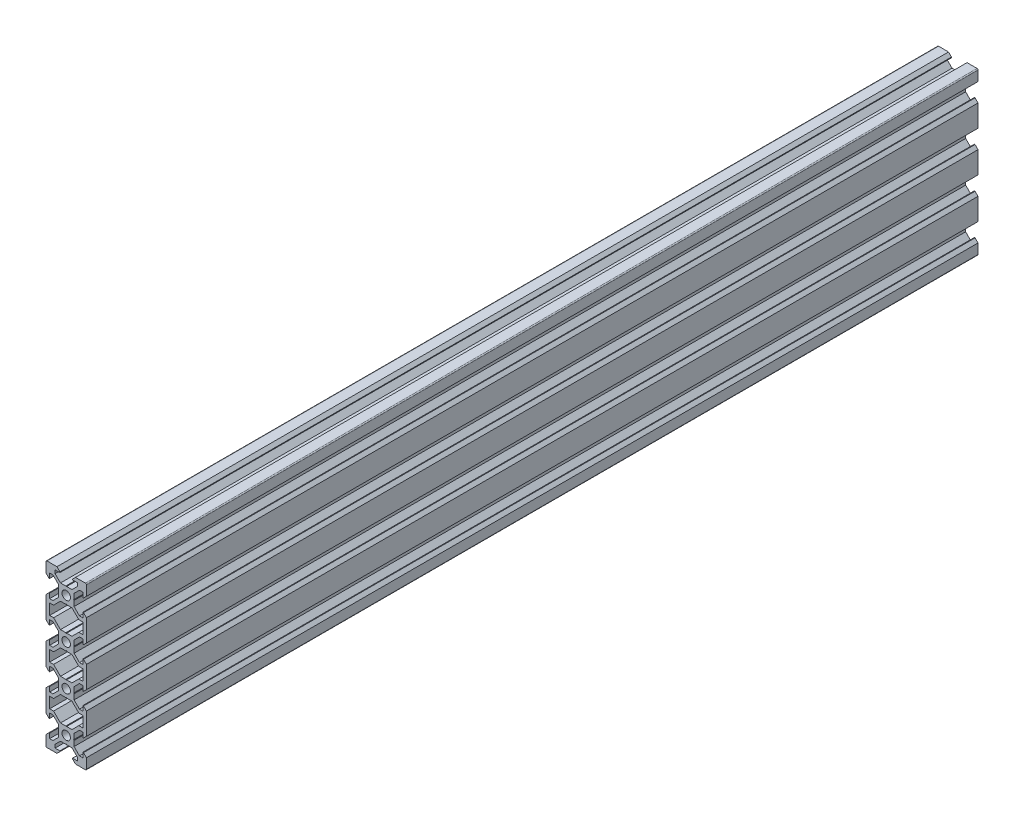
SolidWorks part; units mm, degrees
ref_plane "Plan de face" through (0, 0, 0) normal (0, 0, 1) x (1, 0, 0)
ref_plane "Plan de dessus" through (0, 0, 0) normal (0, 1, 0) x (1, 0, 0)
ref_plane "Plan de droite" through (0, 0, 0) normal (1, 0, 0) x (0, 0, -1)
ref_axis "Axe" through (0, 0, -13.782) along (0, 0, 1)
sketch "Esquisse1" plane through (0, 0, 0) normal (0, 0, 1) x (1, 0, 0)
  line L0 (0, 27.6392) -> (0, -27.6392) construction
  line L1 (-33.6074, 0) -> (33.6074, 0) construction
  line L2 (0, 0) -> (-22.2114, 22.2114) construction
  line L3 (-9.5, 10) -> (-4.58, 10)
  line L4 (-4.58, 10) -> (-3.125, 8.545)
  line L5 (-3.125, 8.545) -> (-3.125, 8.2)
  line L6 (-3.125, 8.2) -> (-5.5, 8.2)
  line L7 (-2.8393, 3.9) -> (-5.5, 6.5607)
  line L8 (-2.8393, 3.9) -> (-0.21, 3.9)
  line L9 (-5.5, 6.5607) -> (-5.5, 8.2)
  line L10 (0, 3.69) -> (0, 2.1)
  line L11 (-3.9, 2.8393) -> (-6.5607, 5.5)
  line L12 (-8.545, 3.125) -> (-8.2, 3.125)
  line L13 (-8.2, 3.125) -> (-8.2, 5.5)
  line L14 (-6.5607, 5.5) -> (-8.2, 5.5)
  line L15 (-10, 4.58) -> (-8.545, 3.125)
  line L16 (-10, 9.5) -> (-10, 4.58)
  line L17 (-0.21, 3.9) -> (0, 3.69)
  line L18 (-3.9, 2.8393) -> (-3.9, 0.21)
  line L19 (-6.2393, -12.7) -> (-8.2, -12.7)
  line L20 (-3.9, 0.21) -> (-3.69, 0)
  line L21 (-0.21, -3.9) -> (0, -3.69)
  line L22 (0, -3.69) -> (0, -2.1)
  line L23 (-6.5607, -5.5) -> (-8.2, -5.5)
  line L24 (-2.8393, -3.9) -> (-0.21, -3.9)
  line L25 (-8.545, -3.125) -> (-8.2, -3.125)
  line L26 (-10, -4.58) -> (-8.545, -3.125)
  line L27 (-8.2, -3.125) -> (-8.2, -5.5)
  line L28 (-2.8393, -3.9) -> (-6.2393, -7.3)
  line L29 (-3.9, -2.8393) -> (-6.5607, -5.5)
  line L30 (-3.9, -2.8393) -> (-3.9, -0.21)
  line L31 (-3.9, -0.21) -> (-3.69, 0)
  line L32 (-6.2393, -7.3) -> (-8.2, -7.3)
  line L33 (-8.2, -7.3) -> (-8.2, -12.7)
  line L34 (-8.2, -10) -> (-10, -10) construction
  line L35 (-10, -15.42) -> (-10, -4.58)
  line L36 (-3.9, -19.79) -> (-3.69, -20)
  line L37 (-3.9, -17.1607) -> (-3.9, -19.79)
  line L38 (-3.9, -17.1607) -> (-6.5607, -14.5)
  line L39 (-2.8393, -16.1) -> (-6.2393, -12.7)
  line L40 (-8.2, -16.875) -> (-8.2, -14.5)
  line L41 (-10, -15.42) -> (-8.545, -16.875)
  line L42 (-8.545, -16.875) -> (-8.2, -16.875)
  line L43 (-2.8393, -16.1) -> (-0.21, -16.1)
  line L44 (-6.5607, -14.5) -> (-8.2, -14.5)
  line L45 (0, -16.31) -> (0, -17.9)
  line L46 (-0.21, -16.1) -> (0, -16.31)
  line L47 (-8.2, -30) -> (-10, -30) construction
  line L48 (-3.69, -20) -> (0, -20) construction
  line L49 (-0.21, -23.9) -> (0, -23.69)
  line L50 (0, -23.69) -> (0, -22.1)
  line L51 (-6.5607, -25.5) -> (-8.2, -25.5)
  line L52 (-2.8393, -23.9) -> (-0.21, -23.9)
  line L53 (-8.545, -23.125) -> (-8.2, -23.125)
  line L54 (-10, -24.58) -> (-8.545, -23.125)
  line L55 (-8.2, -23.125) -> (-8.2, -25.5)
  line L56 (-2.8393, -23.9) -> (-6.2393, -27.3)
  line L57 (-3.9, -22.8393) -> (-6.5607, -25.5)
  line L58 (-3.9, -22.8393) -> (-3.9, -20.21)
  line L59 (-3.9, -20.21) -> (-3.69, -20)
  line L60 (-10, -24.58) -> (-10, -35.42)
  line L61 (-8.2, -32.7) -> (-8.2, -27.3)
  line L62 (-3.69, -40) -> (0, -40) construction
  line L63 (-8.2, -50) -> (-10, -50) construction
  line L64 (0, -60) -> (-22.2114, -82.2114) construction
  line L65 (-33.6074, -60) -> (33.6074, -60) construction
  line L66 (0, -87.6392) -> (0, -32.3608) construction
  line L67 (-6.2393, -32.7) -> (-8.2, -32.7)
  line L68 (-3.9, -39.79) -> (-3.69, -40)
  line L69 (-3.9, -37.1607) -> (-3.9, -39.79)
  line L70 (-3.9, -37.1607) -> (-6.5607, -34.5)
  line L71 (-2.8393, -36.1) -> (-6.2393, -32.7)
  line L72 (-8.2, -36.875) -> (-8.2, -34.5)
  line L73 (-10, -35.42) -> (-8.545, -36.875)
  line L74 (-8.545, -36.875) -> (-8.2, -36.875)
  line L75 (-6.2393, -27.3) -> (-8.2, -27.3)
  line L76 (-2.8393, -36.1) -> (-0.21, -36.1)
  line L77 (-6.5607, -34.5) -> (-8.2, -34.5)
  line L78 (0, -36.31) -> (0, -37.9)
  line L79 (-0.21, -36.1) -> (0, -36.31)
  line L80 (-0.21, -43.9) -> (0, -43.69)
  line L81 (0, -43.69) -> (0, -42.1)
  line L82 (-6.5607, -45.5) -> (-8.2, -45.5)
  line L83 (-2.8393, -43.9) -> (-0.21, -43.9)
  line L84 (-8.545, -43.125) -> (-8.2, -43.125)
  line L85 (-10, -44.58) -> (-8.545, -43.125)
  line L86 (-8.2, -43.125) -> (-8.2, -45.5)
  line L87 (-2.8393, -43.9) -> (-6.2393, -47.3)
  line L88 (-3.9, -42.8393) -> (-6.5607, -45.5)
  line L89 (-3.9, -42.8393) -> (-3.9, -40.21)
  line L90 (-3.9, -40.21) -> (-3.69, -40)
  line L91 (-10, -44.58) -> (-10, -55.42)
  line L92 (-8.2, -52.7) -> (-8.2, -47.3)
  line L93 (-6.2393, -52.7) -> (-8.2, -52.7)
  line L94 (-3.9, -59.79) -> (-3.69, -60)
  line L95 (-3.9, -57.1607) -> (-3.9, -59.79)
  line L96 (-3.9, -57.1607) -> (-6.5607, -54.5)
  line L97 (-2.8393, -56.1) -> (-6.2393, -52.7)
  line L98 (-8.2, -56.875) -> (-8.2, -54.5)
  line L99 (-10, -55.42) -> (-8.545, -56.875)
  line L100 (-8.545, -56.875) -> (-8.2, -56.875)
  line L101 (-2.8393, -56.1) -> (-0.21, -56.1)
  line L102 (-6.5607, -54.5) -> (-8.2, -54.5)
  line L103 (0, -56.31) -> (0, -57.9)
  line L104 (-0.21, -56.1) -> (0, -56.31)
  line L105 (-3.9, -60.21) -> (-3.69, -60)
  line L106 (-6.2393, -47.3) -> (-8.2, -47.3)
  line L107 (-3.9, -62.8393) -> (-3.9, -60.21)
  line L108 (-0.21, -63.9) -> (0, -63.69)
  line L109 (-10, -69.5) -> (-10, -64.58)
  line L110 (-10, -64.58) -> (-8.545, -63.125)
  line L111 (-6.5607, -65.5) -> (-8.2, -65.5)
  line L112 (-8.2, -63.125) -> (-8.2, -65.5)
  line L113 (-8.545, -63.125) -> (-8.2, -63.125)
  line L114 (-3.9, -62.8393) -> (-6.5607, -65.5)
  line L115 (0, -63.69) -> (0, -62.1)
  line L116 (-5.5, -66.5607) -> (-5.5, -68.2)
  line L117 (-2.8393, -63.9) -> (-0.21, -63.9)
  line L118 (-2.8393, -63.9) -> (-5.5, -66.5607)
  line L119 (-3.125, -68.2) -> (-5.5, -68.2)
  line L120 (-3.125, -68.545) -> (-3.125, -68.2)
  line L121 (-4.58, -70) -> (-3.125, -68.545)
  line L122 (-9.5, -70) -> (-4.58, -70)
  arc A0 (0, -2.1) -> (0, 2.1) centre (0, 0) cw
  arc A1 (-9.5, 10) -> (-10, 9.5) centre (-9.5, 9.5) ccw
  arc A2 (0, -42.1) -> (0, -37.9) centre (0, -40) cw
  arc A3 (-9.5, -70) -> (-10, -69.5) centre (-9.5, -69.5) cw
  arc A4 (0, -17.9) -> (0, -22.1) centre (0, -20) ccw
  arc A5 (0, -57.9) -> (0, -62.1) centre (0, -60) ccw
  point P4 (0, 0)
  point P7 (0, 0)
  point P30 (-10, 10)
  point P60 (0, -20)
  point P146 (-10, -70)
  dimension "D5" = 11
  dimension "D2" = 2.1
  dimension "D3" = 6.25
  dimension "D10" = 0.5
  dimension "D4" = 9.16
  dimension "D6" = 1.5
  dimension "D7" = 1.8
  dimension "D8" = 4.3
  dimension "D9" = 20
  dimension "D11" = 0.42
  dimension "D12" = 10
  dimension "D13" = 1.8
extrude "Boss.-Extru.1" add sketch "Esquisse1" along normal blind 441.2
sketch "Esquisse3" plane through (0, 0, 441.2) normal (0, 0, 1) x (1, 0, 0)
  line L0 (0, 0) -> (-9.8536, 9.8536) construction
  line L1 (-8.2, 8.2) -> (-8.2, 6.57)
  line L2 (-8.2, 6.57) -> (-7.54, 6.57)
  line L3 (-7.54, 6.57) -> (-6.57, 7.54)
  line L4 (-8.2, 3.125) -> (-8.2, 5.5) construction
  line L5 (-6.57, 8.2) -> (-6.57, 7.54)
  line L6 (-8.2, 8.2) -> (-6.57, 8.2)
  line L7 (-5.5, 6.5607) -> (-5.5, 8.2) construction
  line L8 (-10, -30) -> (6.918, -30) construction
  line L9 (-10, -24.58) -> (-10, -35.42) construction
  line L10 (-8.2, -68.2) -> (-6.57, -68.2)
  line L11 (-6.57, -68.2) -> (-6.57, -67.54)
  line L12 (-7.54, -66.57) -> (-6.57, -67.54)
  line L13 (-8.2, -66.57) -> (-7.54, -66.57)
  line L14 (-8.2, -68.2) -> (-8.2, -66.57)
  arc A0 (-9.5, 10) -> (-10, 9.5) centre (-9.5, 9.5) ccw construction
  point P13 (-7.055, 7.055)
  point P14 (-6.57, 7.87)
  point P26 (-7.055, -67.055)
  dimension "D1" = 1.07
extrude "Enlèv. mat.-Extru.1" [suppressed] cut sketch "Esquisse3" against normal through all
mirror "Symétrie1" about plane through (0, 3.69, 441.2) normal (-1, 0, 0) of "Enlèv. mat.-Extru.1", "Boss.-Extru.1"
